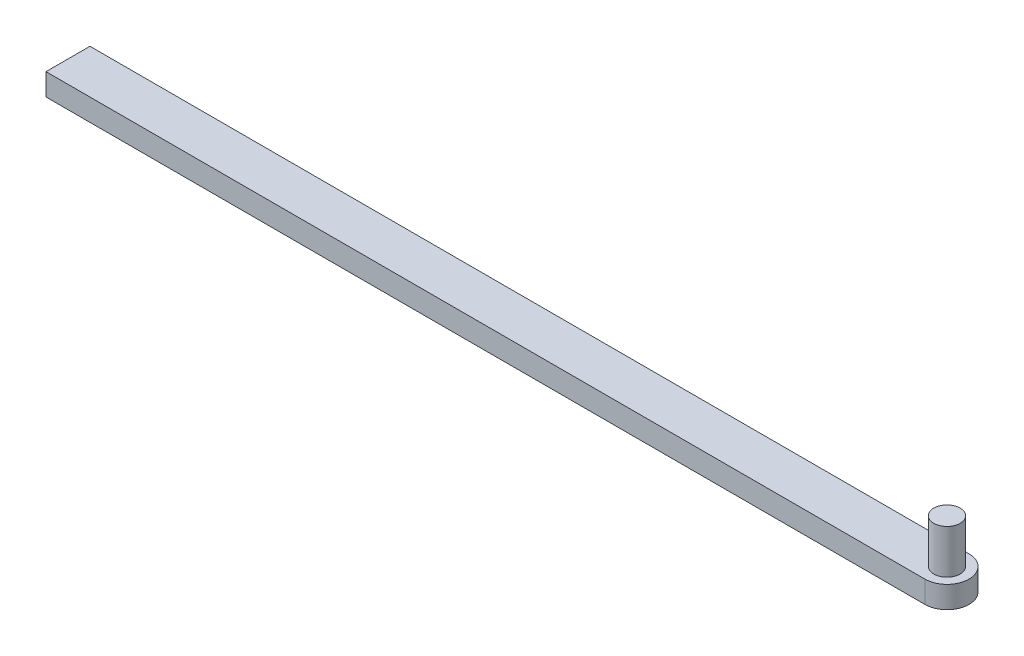
SolidWorks part; units mm, degrees
ref_plane "前视基准面" through (0, 0, 0) normal (0, 0, 1) x (1, 0, 0)
ref_plane "上视基准面" through (0, 0, 0) normal (0, 1, 0) x (1, 0, 0)
ref_plane "右视基准面" through (0, 0, 0) normal (1, 0, 0) x (0, 0, -1)
sketch "草图1" plane through (0, 0, 0) normal (0, 1, 0) x (1, 0, 0)
  line L0 (0, 0) -> (200, 0)
  line L1 (0, 0) -> (0, -10)
  line L2 (200, -10) -> (0, -10)
  arc A1 (200, -10) -> (200, 0) centre (200, -5) ccw
  dimension "D1" = 200
  dimension "D2" = 5
extrude "凸台-拉伸1" add sketch "草图1" along normal blind 5
sketch "草图2" plane through (0, 5, 0) normal (0, 1, 0) x (1, 0, 0)
  line L0 (200, 0) -> (200, -10) construction
  circle A0 centre (200, -5) radius 3
extrude "凸台-拉伸2" add sketch "草图2" along normal blind 10
